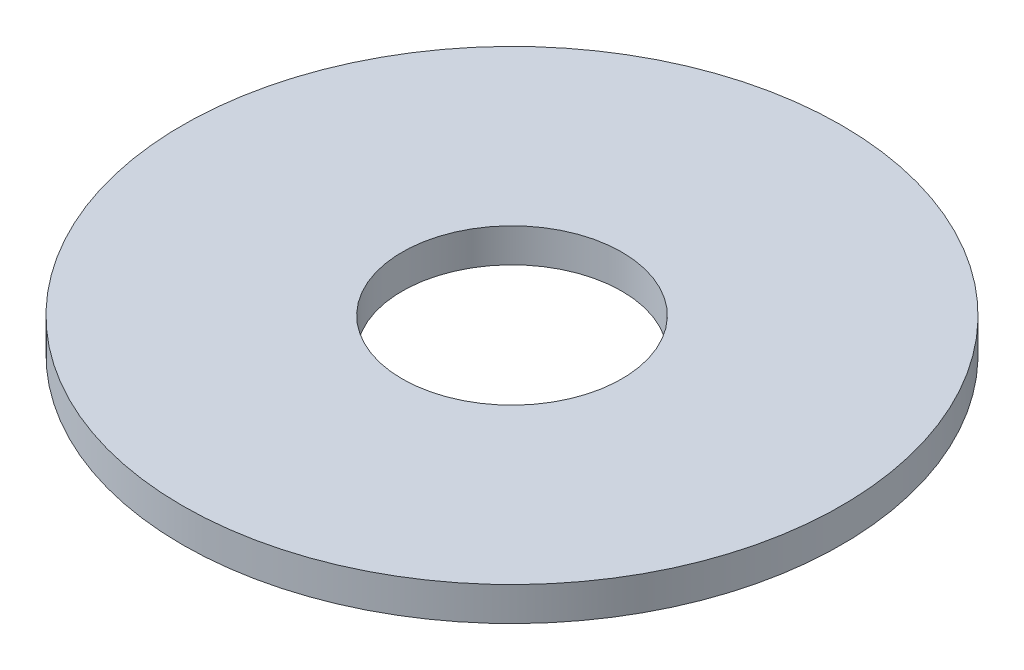
SolidWorks part; units mm, degrees
ref_plane "Front Plane" through (0, 0, 0) normal (0, 0, 1) x (1, 0, 0)
ref_plane "Top Plane" through (0, 0, 0) normal (0, 1, 0) x (1, 0, 0)
ref_plane "Right Plane" through (0, 0, 0) normal (1, 0, 0) x (0, 0, -1)
sketch "Sketch1" plane through (0, 0, 0) normal (0, 1, 0) x (1, 0, 0)
  circle A0 centre (0, 0) radius 97.5
  dimension "FLANGE_OD" = 195
extrude "Boss-Extrude1" add sketch "Sketch1" along normal blind 10
sketch "Sketch2" plane through (0, 0, 0) normal (0, 1, 0) x (1, 0, 0)
  circle A0 centre (0, 0) radius 32.5
  dimension "BORE_D" = 65
extrude "Cut-Extrude1" cut sketch "Sketch2" along normal through all
sketch "Sketch3" plane through (0, 10, 0) normal (0, 1, 0) x (1, 0, 0)
  circle A0 centre (0, 0) radius 22.0622 construction
  circle A1 centre (-22.0622, 0) radius 5.9377
  dimension "BOLT_D" = 11.8753
  dimension "BOLT_PCD" = 44.1245
extrude "Cut-Extrude2" cut sketch "Sketch3" against normal blind 7.7366 rebuild error yes
pattern_circular "CirPattern1" count 8 over 360 rebuild error yes
